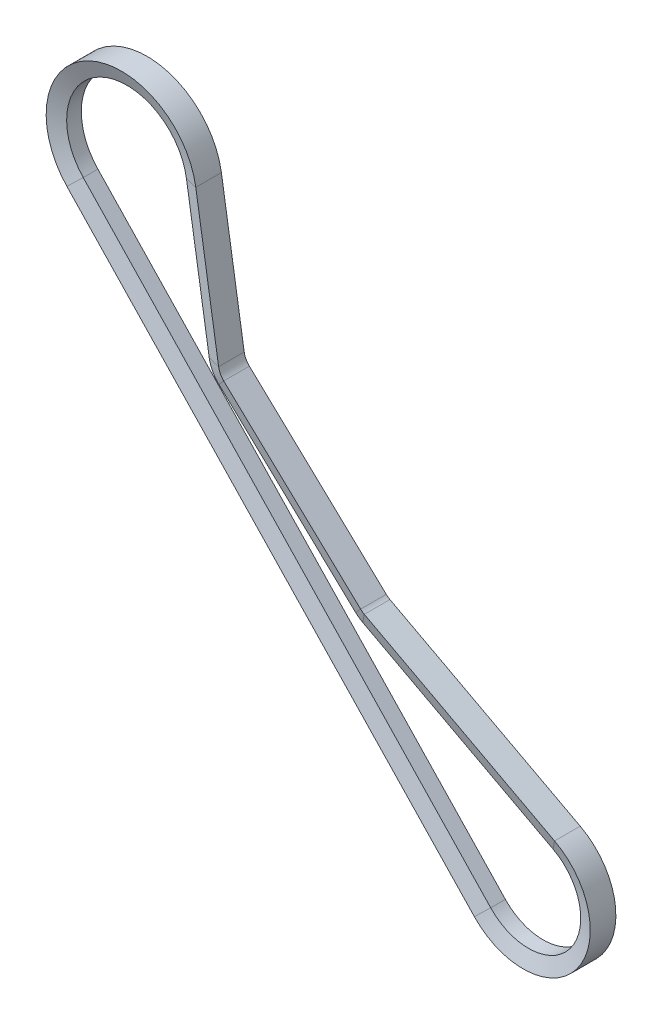
SolidWorks part; units mm, degrees
ref_plane "Front Plane" through (0, 0, 0) normal (0, 0, 1) x (1, 0, 0)
ref_plane "Top Plane" through (0, 0, 0) normal (0, 1, 0) x (1, 0, 0)
ref_plane "Right Plane" through (0, 0, 0) normal (1, 0, 0) x (0, 0, -1)
sketch "Sketch2" plane through (0, 0, 0) normal (0, 0, 1) x (1, 0, 0)
  line L0 (0, 0) -> (1, 0) construction
  line L1 (0, 0) -> (0, 1) construction
  line L12 (-18.1205, -17.2234) -> (-169.6725, 142.2225)
  line L14 (-121.7227, 165.8954) -> (-113.2368, 112.3495)
  line L15 (-111.3239, 108.7257) -> (-60.4198, 60.676)
  line L16 (-59.0409, 59.6863) -> (11.7318, 22.0763)
  arc A4 (-169.6725, 142.2225) -> (-121.7227, 165.8954) centre (-149.3775, 161.5127) cw
  arc A7 (11.7318, 22.0763) -> (-18.1205, -17.2234) centre (0, 0) cw
  arc A8 (-113.2368, 112.3495) -> (-111.3239, 108.7257) centre (-106.9651, 113.3434) ccw
  arc A9 (-60.4198, 60.676) -> (-59.0409, 59.6863) centre (-56.061, 65.2937) ccw
ref_plane "Plane4" through (11.7318, 22.0763, 0) normal (0.8831, -0.4693, 0) x (-0.4693, -0.8831, 0)
sketch "Sketch3" plane through (11.7318, 22.0763, 0) normal (0.8831, -0.4693, 0) x (-0.4693, -0.8831, 0)
  line L0 (0, -4.7625) -> (0, 4.7625)
  line L1 (0, -4.7625) -> (5.588, -2.7286)
  line L2 (5.588, -2.7286) -> (5.588, 2.7286)
  line L3 (5.588, 2.7286) -> (0, 4.7625)
  line L4 (0, 0) -> (5.588, 0) construction
  dimension "D1" = 9.525
  dimension "D2" = 5.588
  dimension "D3" = 40
sweep "Sweep1" add profiles "Sketch3" path "Sketch2"
